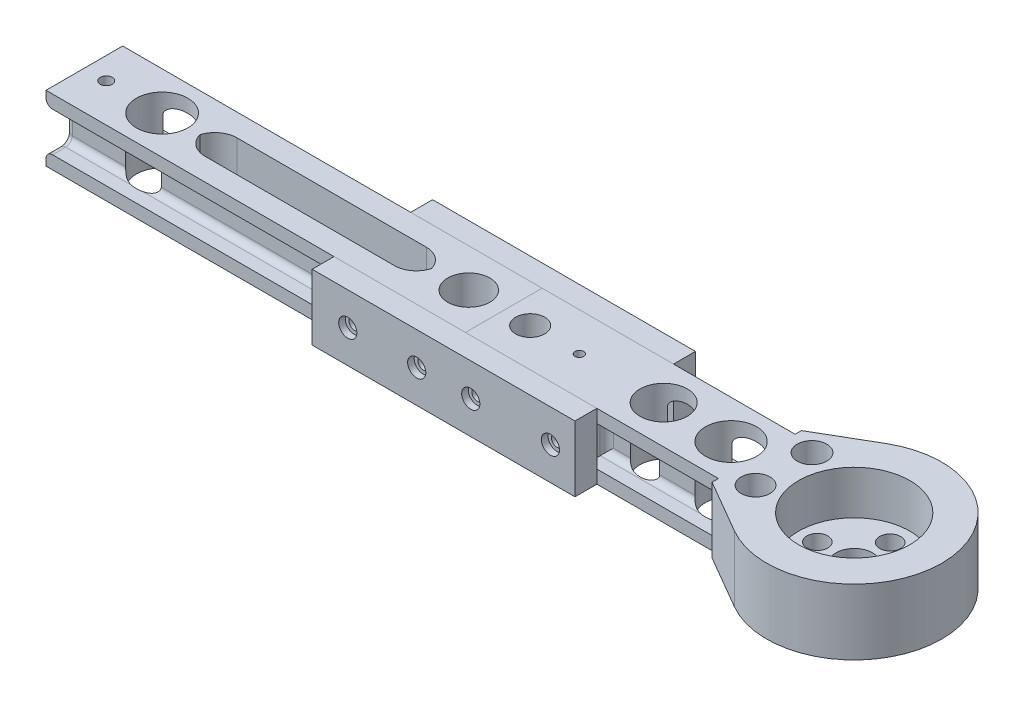
SolidWorks part; units mm, degrees
material "PLA "
ref_plane "Front Plane" through (0, 0, 0) normal (0, 0, 1) x (1, 0, 0)
ref_plane "Top Plane" through (0, 0, 0) normal (0, 1, 0) x (1, 0, 0)
ref_plane "Right Plane" through (0, 0, 0) normal (1, 0, 0) x (0, 0, -1)
sketch "Sketch1" plane through (0, 0, 0) normal (0, 1, 0) x (1, 0, 0)
  line L0 (0, 0) -> (-247, 0) construction
  line L1 (-247, 0) -> (-447, 0) construction
  dimension "D1" = 247
  dimension "D2" = 200
sketch "Sketch2" plane through (0, 0, 0) normal (0, 1, 0) x (1, 0, 0)
  line L1 (-247, -17.5) -> (0, -17.5)
  line L2 (-247, -17.5) -> (-247, 17.5)
  line L3 (-247, 17.5) -> (0, 17.5)
  line L4 (0, -17.5) -> (0, 17.5)
  point P4 (-247, 0)
  dimension "D1" = 35
extrude "Boss-Extrude1" add sketch "Sketch2" along normal blind 30 contours L1 L4 L3 L2
sketch "Sketch3" plane through (0, 0, 0) normal (0, -1, 0) x (1, 0, 0)
  line L0 (0, 0) -> (-21, 0) construction
  line L1 (0, 0) -> (-247, 0) construction
  circle A0 centre (-21, 0) radius 5.6
  dimension "D2" = 11.2
  dimension "D1" = 21
extrude "Cut-Extrude1" cut sketch "Sketch3" against normal through all
sketch "Sketch4" plane through (0, 30, 0) normal (0, 1, 0) x (1, 0, 0)
  line L0 (0, -17.5) -> (0, 17.5) construction
  line L1 (-14.9, 3.5218) -> (-21, 7.0437)
  line L2 (-21, 7.0437) -> (-27.1, 3.5218)
  line L3 (-27.1, 3.5218) -> (-27.1, -3.5218)
  line L4 (-27.1, -3.5218) -> (-21, -7.0437)
  line L5 (-21, -7.0437) -> (-14.9, -3.5218)
  line L6 (-14.9, -3.5218) -> (-14.9, 3.5218)
  line L7 (-27.1, 0) -> (-14.9, 0)
  circle A0 centre (-21, 0) radius 6.1 construction
  dimension "D1" = 12.2
extrude "Cut-Extrude2" cut sketch "Sketch4" against normal blind 22 contours L1 L2 L3 L4 L5 L6
sketch "Sketch5" plane through (0, 0, 0) normal (1, 0, 0) x (0, 0, -1)
  line L0 (0, 8) -> (0, 1) construction
  line L1 (-3.5218, 8) -> (3.5218, 8) construction
  line L2 (0, 1) -> (0, -2.0977) construction
  line L3 (2.5, 1) -> (2.5, -2.0977)
  line L4 (-2.5, 1) -> (-2.5, -2.0977)
  arc A0 (2.5, 1) -> (-2.5, 1) centre (0, 1) ccw
  arc A1 (-2.5, -2.0977) -> (2.5, -2.0977) centre (0, -2.0977) ccw
  point P5 (0, -0.5488)
  dimension "D1" = 7
  dimension "D2" = 5
sketch "Sketch6" plane through (0, 0, 0) normal (1, 0, 0) x (0, 0, -1)
  line L0 (0, 8) -> (0, 16) construction
  line L1 (-3.5218, 8) -> (3.5218, 8) construction
  line L2 (-17.5, 30) -> (17.5, 30) construction
  line L3 (-11.0435, 16) -> (11.453, 16)
  line L4 (-11.0435, 16) -> (-11.0435, 30)
  line L5 (-11.0435, 30) -> (11.453, 30)
  line L6 (11.453, 16) -> (11.453, 30)
  dimension "D1" = 8
extrude "Boss-Extrude3" add sketch "Sketch6" against normal blind 38
sketch "Sketch7" plane through (0, 0, 17.5) normal (0, 0, 1) x (1, 0, 0)
  line L0 (-21, 16) -> (-14.9, 16) construction
  line L1 (-27.1, 16) -> (-21, 16) construction
  line L2 (-27.1, 8) -> (-27.1, 16) construction
  line L3 (-14.9, 8) -> (-14.9, 16) construction
  line L4 (-15.4, 0) -> (-15.4, 8) construction
  line L5 (-26.6, 8) -> (-26.6, 0) construction
  line L6 (-21, 16) -> (-14.9, 16)
  line L7 (-27.1, 16) -> (-21, 16)
  line L8 (-27.1, 8) -> (-27.1, 16)
  line L9 (-14.9, 8) -> (-14.9, 16)
  line L10 (-15.4, 0) -> (-15.4, 8)
  line L11 (-26.6, 8) -> (-26.6, 0)
  line L12 (-27.1, 8) -> (-26.6, 8)
  line L13 (-15.4, 8) -> (-14.9, 8)
  line L14 (-26.6, 0) -> (-15.4, 0)
extrude "Cut-Extrude4" cut sketch "Sketch7" against normal up to vertex (17.5 mm away) up to point (-14.9, 30, 0)
sketch "Sketch9" plane through (0, 30, 0) normal (0, 1, 0) x (1, 0, 0)
  line L0 (-27.1, 3.5218) -> (-14.9, -3.5218) construction
  line L1 (-27.1, -3.5218) -> (-14.9, 3.5218) construction
  line L6 (-14.9, 3.5218) -> (-21, 7.0437)
  line L7 (-21, 7.0437) -> (-27.1, 3.5218)
  line L8 (-27.1, 3.5218) -> (-27.1, -3.5218)
  line L9 (-27.1, -3.5218) -> (-21, -7.0437)
  line L10 (-21, -7.0437) -> (-14.9, -3.5218)
  line L11 (-14.9, -3.5218) -> (-14.9, 3.5218)
  line L12 (-14.9, 3.5218) -> (-21, 7.0437) construction
  line L13 (-21, 7.0437) -> (-27.1, 3.5218) construction
  line L14 (-27.1, 3.5218) -> (-27.1, -3.5218) construction
  line L15 (-27.1, -3.5218) -> (-21, -7.0437) construction
  line L16 (-21, -7.0437) -> (-14.9, -3.5218) construction
  line L17 (-14.9, -3.5218) -> (-14.9, 3.5218) construction
  circle A0 centre (-21, 0) radius 2
  dimension "D2" = 4
  dimension "D1" = 0
extrude "Cut-Extrude5" cut sketch "Sketch9" against normal blind 38
sketch "Sketch15" plane through (0, 30, 0) normal (0, 1, 0) x (1, 0, 0)
  line L0 (-247, 0) -> (-237, 0) construction
  line L1 (0, 0) -> (-247, 0) construction
  circle A0 centre (-237, 0) radius 2.75
  dimension "D2" = 5.5
  dimension "D1" = 10
extrude "Cut-Extrude10" cut sketch "Sketch15" against normal blind 9
sketch "Sketch16" plane through (0, 0, 0) normal (0, -1, 0) x (1, 0, 0)
  line L1 (-241.1302, 2.6504) -> (-241.3604, -2.2517)
  line L2 (-241.3604, -2.2517) -> (-237.2302, -4.9021)
  line L3 (-237.2302, -4.9021) -> (-232.8698, -2.6504)
  line L4 (-232.8698, -2.6504) -> (-232.6396, 2.2517)
  line L5 (-232.6396, 2.2517) -> (-236.7698, 4.9021)
  line L6 (-236.7698, 4.9021) -> (-241.1302, 2.6504)
  circle A0 centre (-237, 0) radius 2.75 construction
  circle A1 centre (-237, 0) radius 2.75 construction
  circle A2 centre (-237, 0) radius 4.25 construction
  dimension "D1" = 8.5
extrude "Cut-Extrude11" cut sketch "Sketch16" against normal up to surface (21 mm away) up to face at (-237, 21, 2.75)
sketch "Sketch17" plane through (0, 30, 0) normal (0, 1, 0) x (1, 0, 0)
  line L0 (0, 0) -> (-247, 0) construction
  line L2 (-58.6673, -9.5384) -> (-188.3327, -9.5384)
  line L3 (-58.6673, -9.5384) -> (-58.6673, 9.5384)
  line L4 (-58.6673, 9.5384) -> (-188.3327, 9.5384)
  line L5 (-188.3327, -9.5384) -> (-188.3327, 9.5384)
  line L6 (-58.6673, -9.5384) -> (-188.3327, 9.5384) construction
  line L7 (-58.6673, 9.5384) -> (-188.3327, -9.5384) construction
  point P4 (-123.5, 0)
extrude "Cut-Extrude12" [suppressed] cut sketch "Sketch17" against normal through all
fillet "Fillet1" [suppressed] radius 10
sketch "Sketch19" plane through (0, 0, 0) normal (1, 0, 0) x (0, 0, -1)
  line L5 (17.5, 0) -> (17.5, 30)
  line L6 (17.5, 30) -> (-17.5, 30)
  line L7 (-17.5, 30) -> (-17.5, 0)
  line L8 (-17.5, 0) -> (17.5, 0)
  line L9 (17.5, 0) -> (17.5, 30)
  line L10 (17.5, 30) -> (-17.5, 30)
  line L11 (-17.5, 30) -> (-17.5, 0)
  line L12 (-17.5, 0) -> (17.5, 0)
  dimension "D1" = 0
extrude "Boss-Extrude5" add sketch "Sketch19" along normal blind 55
sketch "Sketch18" plane through (0, 30, 0) normal (0, 1, 0) x (1, 0, 0)
  line L0 (84.4055, -34.5857) -> (84.4055, 34.5857) construction
  line L1 (55, 17.5) -> (55, -17.5)
  line L2 (55, -17.5) -> (84.4055, -34.5857)
  line L5 (84.4055, 34.5857) -> (55, 17.5)
  line L6 (55, 0) -> (84.4055, 0) construction
  arc A1 (84.4055, -34.5857) -> (84.4055, 34.5857) centre (104.5011, 0) ccw
  point P7 (144.5011, 0)
  dimension "D1" = 40
extrude "Boss-Extrude4" add sketch "Sketch18" against normal up to vertex (30 mm away)
sketch "Sketch20" plane through (0, 0, 0) normal (0, -1, 0) x (1, 0, 0)
  circle A0 centre (104.5011, 0) radius 25.4
  dimension "D1" = 50.8
sketch "Sketch21" plane through (0, 30, 0) normal (0, 1, 0) x (1, 0, 0)
  circle A1 centre (104.5011, 0) radius 25.4
  circle A2 centre (104.5011, 0) radius 25.4
  dimension "D1" = 0
extrude "Cut-Extrude14" cut sketch "Sketch21" against normal blind 20
sketch "Sketch22" plane through (0, 0, 0) normal (0, -1, 0) x (1, 0, 0)
  line L0 (-247, 0) -> (144.5011, 0) construction
  arc A0 (84.4055, -34.5857) -> (84.4055, 34.5857) centre (104.5011, 0) ccw construction
  point P6 (-21, 0)
sketch "Sketch23" plane through (0, 0, 17.5) normal (0, 0, 1) x (1, 0, 0)
  line L0 (-55.4989, 91.556) -> (-55.4989, -31.556)
  line L3 (144.5011, 0) -> (144.5011, 64.4466) construction
  line L4 (-27.1, 16) -> (-27.1, 55.3644) construction
  point P3 (-55.4989, 30)
  dimension "D1" = 200
split "Split1" trim tools "Sketch23" bodies to split 118 resulting bodies 119 120
sketch "Sketch24" plane through (0, 0, 17.5) normal (0, 0, 1) x (1, 0, 0)
  line L0 (-55.4989, 30) -> (-55.4989, 0) construction
  line L1 (0, 0) -> (-247, 0) construction
  line L2 (-55.4989, 91.556) -> (-55.4989, -31.556) construction
  line L3 (-55.4989, 0) -> (-55.4989, 15) construction
  line L4 (-55.4989, 30) -> (55, 30) construction
  line L5 (-115.4989, 0) -> (4.5011, 0)
  line L6 (-115.4989, 0) -> (-115.4989, 30)
  line L7 (-115.4989, 30) -> (4.5011, 30)
  line L8 (4.5011, 0) -> (4.5011, 30)
  line L9 (-115.4989, 0) -> (4.5011, 30) construction
  line L10 (-115.4989, 30) -> (4.5011, 0) construction
  dimension "D1" = 120
extrude "Boss-Extrude6" add sketch "Sketch24" along normal blind 10 separate body contours L6 L7 L8 L5
sketch "Sketch26" plane through (0, 0, -17.5) normal (0, 0, -1) x (-1, 0, 0)
  line L4 (-4.5011, 0) -> (115.4989, 0)
  line L5 (-4.5011, 30) -> (-4.5011, 0)
  line L6 (115.4989, 30) -> (-4.5011, 30)
  line L7 (115.4989, 0) -> (115.4989, 30)
  line L8 (-4.5011, 0) -> (115.4989, 0)
  line L9 (-4.5011, 30) -> (-4.5011, 0)
  line L10 (115.4989, 30) -> (-4.5011, 30)
  line L11 (115.4989, 0) -> (115.4989, 30)
  dimension "D1" = 0
extrude "Boss-Extrude7" add sketch "Sketch26" along normal blind 10 separate body
sketch "Sketch27" plane through (0, 0, -27.5) normal (0, 0, -1) x (-1, 0, 0)
  line L0 (-4.5011, 15) -> (115.4989, 15) construction
  line L1 (-4.5011, 30) -> (-4.5011, 0) construction
  line L2 (115.4989, 0) -> (115.4989, 30) construction
  circle A0 centre (43.074, 15) radius 2.5
  circle A1 centre (67.7461, 15) radius 2.5
  circle A2 centre (99.2164, 15) radius 2.5
  circle A3 centre (6.7066, 15) radius 2.5
  dimension "D1" = 5
extrude "Cut-Extrude15" cut sketch "Sketch27" against normal through all
sketch "Sketch31" plane through (0, 0, -27.5) normal (0, 0, -1) x (-1, 0, 0)
  line L1 (45.4412, 10.9) -> (47.8083, 15)
  line L2 (47.8083, 15) -> (45.4412, 19.1)
  line L3 (45.4412, 19.1) -> (40.7069, 19.1)
  line L4 (40.7069, 19.1) -> (38.3397, 15)
  line L5 (38.3397, 15) -> (40.7069, 10.9)
  line L6 (40.7069, 10.9) -> (45.4412, 10.9)
  line L7 (70.1133, 10.9) -> (72.4804, 15)
  line L8 (72.4804, 15) -> (70.1133, 19.1)
  line L9 (70.1133, 19.1) -> (65.379, 19.1)
  line L10 (65.379, 19.1) -> (63.0119, 15)
  line L11 (63.0119, 15) -> (65.379, 10.9)
  line L12 (65.379, 10.9) -> (70.1133, 10.9)
  line L13 (9.0737, 10.9) -> (11.4408, 15)
  line L14 (11.4408, 15) -> (9.0737, 19.1)
  line L15 (9.0737, 19.1) -> (4.3394, 19.1)
  line L16 (4.3394, 19.1) -> (1.9723, 15)
  line L17 (1.9723, 15) -> (4.3394, 10.9)
  line L18 (4.3394, 10.9) -> (9.0737, 10.9)
  line L19 (101.5835, 10.9) -> (103.9507, 15)
  line L20 (103.9507, 15) -> (101.5835, 19.1)
  line L21 (101.5835, 19.1) -> (96.8493, 19.1)
  line L22 (96.8493, 19.1) -> (94.4821, 15)
  line L23 (94.4821, 15) -> (96.8493, 10.9)
  line L24 (96.8493, 10.9) -> (101.5835, 10.9)
  circle A0 centre (43.074, 15) radius 4.1 construction
  circle A1 centre (67.7461, 15) radius 4.1 construction
  circle A2 centre (6.7066, 15) radius 4.1 construction
  circle A3 centre (99.2164, 15) radius 4.1 construction
  dimension "D1" = 8.2
extrude "Cut-Extrude17" cut sketch "Sketch31" against normal blind 3
sketch "Sketch32" plane through (0, 0, 27.5) normal (0, 0, 1) x (1, 0, 0)
  circle A0 centre (-67.7461, 15) radius 4.15
  circle A1 centre (-43.074, 15) radius 4.15
  circle A2 centre (-99.2164, 15) radius 4.15
  circle A3 centre (-6.7066, 15) radius 4.15
  dimension "D1" = 8.3
extrude "Cut-Extrude18" cut sketch "Sketch32" against normal blind 3
sketch "Sketch28" plane through (-247, 0, 0) normal (-1, 0, 0) x (0, 0, 1)
  line L1 (-17.5, 30) -> (17.5, 30)
  line L2 (-17.5, 30) -> (-17.5, 36.9638)
  line L3 (-17.5, 36.9638) -> (17.5, 36.9638)
  line L4 (17.5, 30) -> (17.5, 36.9638)
extrude "Boss-Extrude8" [suppressed] add sketch "Sketch28" against normal blind 40
sketch "Sketch30" plane through (0, 21, 0) normal (0, -1, 0) x (1, 0, 0)
  circle A0 centre (-237, 0) radius 2.75 construction
  circle A1 centre (-237, 0) radius 2.75
sketch "Sketch33" plane through (-247, 0, 0) normal (-1, 0, 0) x (0, 0, 1)
  line L0 (-17.5, 30) -> (-17.5, 24)
  line L1 (-17.5, 30) -> (-17.5, 0) construction
  line L2 (-17.5, 24) -> (17.5, 24) construction
  line L3 (17.5, 30) -> (17.5, 0) construction
  line L4 (-17.5, 6) -> (17.5, 6) construction
  line L5 (0, 24) -> (0, 6) construction
  line L6 (17.5, 0) -> (17.5, 30) construction
  line L7 (17.5, 0) -> (-17.5, 0) construction
  line L8 (17.5, 30) -> (-17.5, 30) construction
  line L9 (-8.5, 24) -> (-8.5, 6)
  line L10 (8.5, 24) -> (8.5, 6)
  line L11 (-8.5, 15) -> (8.5, 15) construction
  line L12 (-17.5, 24) -> (-8.5, 24)
  line L13 (-8.5, 6) -> (-17.5, 6)
  line L14 (-17.5, 6) -> (-17.5, 0)
  line L15 (-17.5, 0) -> (-17.5, 30) construction
  line L16 (-17.5, 0) -> (17.5, 0)
  line L17 (27.5, 0) -> (17.5, 0) construction
  line L18 (17.5, 0) -> (17.5, 6)
  line L19 (17.5, 6) -> (8.5, 6)
  line L20 (8.5, 24) -> (17.5, 24)
  line L21 (17.5, 24) -> (17.5, 30)
  line L22 (17.5, 30) -> (-17.5, 30)
  line L24 (-24.3906, 37.0172) -> (24.3906, 37.0172)
  line L25 (-24.3906, 37.0172) -> (-24.3906, -7.0172)
  line L26 (-24.3906, -7.0172) -> (24.3906, -7.0172)
  line L27 (24.3906, 37.0172) -> (24.3906, -7.0172)
  line L28 (-24.3906, 37.0172) -> (24.3906, -7.0172) construction
  line L29 (-24.3906, -7.0172) -> (24.3906, 37.0172) construction
  point P9 (0, 24)
  point P12 (0, 6)
  point P24 (0, 15)
  point P25 (0, 15)
  dimension "D1" = 6
  dimension "D2" = 6
  dimension "D3" = 17
extrude "Cut-Extrude19" cut sketch "Sketch33" against normal blind 133 contours L24 L27 L26 L25
sketch "Sketch34" plane through (0, 0, 0) normal (1, 0, 0) x (0, 0, -1)
  line L4 (24.3906, 37.0172) -> (-24.3906, 37.0172)
  line L5 (-24.3906, 37.0172) -> (-24.3906, -7.0172)
  line L6 (-24.3906, -7.0172) -> (24.3906, -7.0172)
  line L7 (24.3906, -7.0172) -> (24.3906, 37.0172)
  line L8 (24.3906, 37.0172) -> (-24.3906, 37.0172)
  line L9 (-24.3906, 37.0172) -> (-24.3906, -7.0172)
  line L10 (-24.3906, -7.0172) -> (24.3906, -7.0172)
  line L11 (24.3906, -7.0172) -> (24.3906, 37.0172)
  line L20 (-17.5, 30) -> (-17.5, 24)
  line L21 (-17.5, 24) -> (-8.5, 24)
  line L22 (-8.5, 24) -> (-8.5, 6)
  line L23 (-8.5, 6) -> (-17.5, 6)
  line L24 (-17.5, 6) -> (-17.5, 0)
  line L25 (-17.5, 0) -> (17.5, 0)
  line L26 (17.5, 0) -> (17.5, 6)
  line L27 (17.5, 6) -> (8.5, 6)
  line L28 (8.5, 6) -> (8.5, 24)
  line L29 (8.5, 24) -> (17.5, 24)
  line L30 (17.5, 24) -> (17.5, 30)
  line L31 (17.5, 30) -> (-17.5, 30)
  line L32 (-17.5, 30) -> (-17.5, 24)
  line L33 (-17.5, 24) -> (-8.5, 24)
  line L34 (-8.5, 24) -> (-8.5, 6)
  line L35 (-8.5, 6) -> (-17.5, 6)
  line L36 (-17.5, 6) -> (-17.5, 0)
  line L37 (-17.5, 0) -> (17.5, 0)
  line L38 (17.5, 0) -> (17.5, 6)
  line L39 (17.5, 6) -> (8.5, 6)
  line L40 (8.5, 6) -> (8.5, 24)
  line L41 (8.5, 24) -> (17.5, 24)
  line L42 (17.5, 24) -> (17.5, 30)
  line L43 (17.5, 30) -> (-17.5, 30)
  dimension "D1" = 0
  dimension "D2" = 0
extrude "Cut-Extrude20" cut sketch "Sketch34" along normal blind 60
fillet "Fillet3" radius 3 12 edges at (-247, 24, 13) (-247, 6, 13) (-247, 6, -13) (-247, 24, -13) (-180.5, 24, 8.5) (-114, 15, 8.5) (-180.5, 6, 8.5) (-247, 15, 8.5) (-180.5, 6, -8.5) (-114, 15, -8.5) (-180.5, 24, -8.5) (-247, 15, -8.5)
fillet "Fillet4" radius 3 8 edges at (60, 15, 8.5) (30, 24, 8.5) (0, 15, 8.5) (30, 6, 8.5) (60, 15, -8.5) (30, 6, -8.5) (0, 15, -8.5) (30, 24, -8.5)
other "Save Bodies1"
sketch "Sketch29" plane through (0, 30, 0) normal (0, 1, 0) x (1, 0, 0)
  line L0 (-88.1262, 0) -> (-194.6695, 0) construction
  line L1 (0, 0) -> (-247, 0) construction
  line L2 (-88.1262, -7.2908) -> (-88.1262, 7.2908)
  line L3 (-88.1262, -7.2908) -> (-194.6695, -7.2908)
  line L4 (-194.6695, -7.2908) -> (-194.6695, 7.2908)
  line L5 (-194.6695, 7.2908) -> (-88.1262, 7.2908)
  point P7 (-88.1262, 0)
extrude "Cut-Extrude16" cut sketch "Sketch29" against normal through all
fillet "Fillet2" radius 10 4 edges at (-194.6695, 15, 7.2908) (-194.6695, 15, -7.2908) (-88.1262, 15, 7.2908) (-88.1262, 15, -7.2908)
other "Save Bodies2"
other "Save Bodies3"
sketch "Sketch35" plane through (0, 30, 0) normal (0, 1, 0) x (1, 0, 0)
  line L0 (0, 0) -> (-247, 0) construction
  line L1 (-247, 0) -> (144.5011, 0) construction
  line L2 (104.5011, 16.4029) -> (104.5011, -16.4029) construction
  circle A0 centre (-211.4939, 0) radius 11.7525
  circle A2 centre (17.4956, 0) radius 10.8299
  circle A3 centre (48.2694, 0) radius 11.6869
  circle A4 centre (71.1334, -11.6869) radius 6.5968
  circle A5 centre (71.1334, 14.0764) radius 6.7566
  circle A6 centre (104.5011, 0) radius 25.4 construction
  circle A7 centre (104.5011, 0) radius 25.4 construction
  circle A8 centre (104.5011, 0) radius 8.2844
  circle A10 centre (104.5011, -16.4029) radius 4.78
  circle A11 centre (87.6729, 0) radius 4.78
  circle A12 centre (121.3646, 0) radius 4.78
  circle A13 centre (104.5011, 16.4029) radius 4.78
  circle A14 centre (-71.485, 0) radius 9.6138
  circle A15 centre (-43.4453, 0) radius 6.6332
  point P31 (104.5011, 0)
extrude "Cut-Extrude22" cut sketch "Sketch35" against normal blind 50
sketch "Sketch36" plane through (0, 0, 17.5) normal (0, 0, 1) x (1, 0, 0)
  line L0 (-21, 8) -> (-21, 0) construction
  line L1 (-15.4, 8) -> (-26.6, 8) construction
sketch "Sketch37" plane through (0, 0, 0) normal (0, -1, 0) x (1, 0, 0)
  circle A0 centre (-21, 0) radius 11.5
  dimension "D1" = 23
extrude "Cut-Extrude23" cut sketch "Sketch37" against normal blind 2
equation "\"2.5c\"=10"
